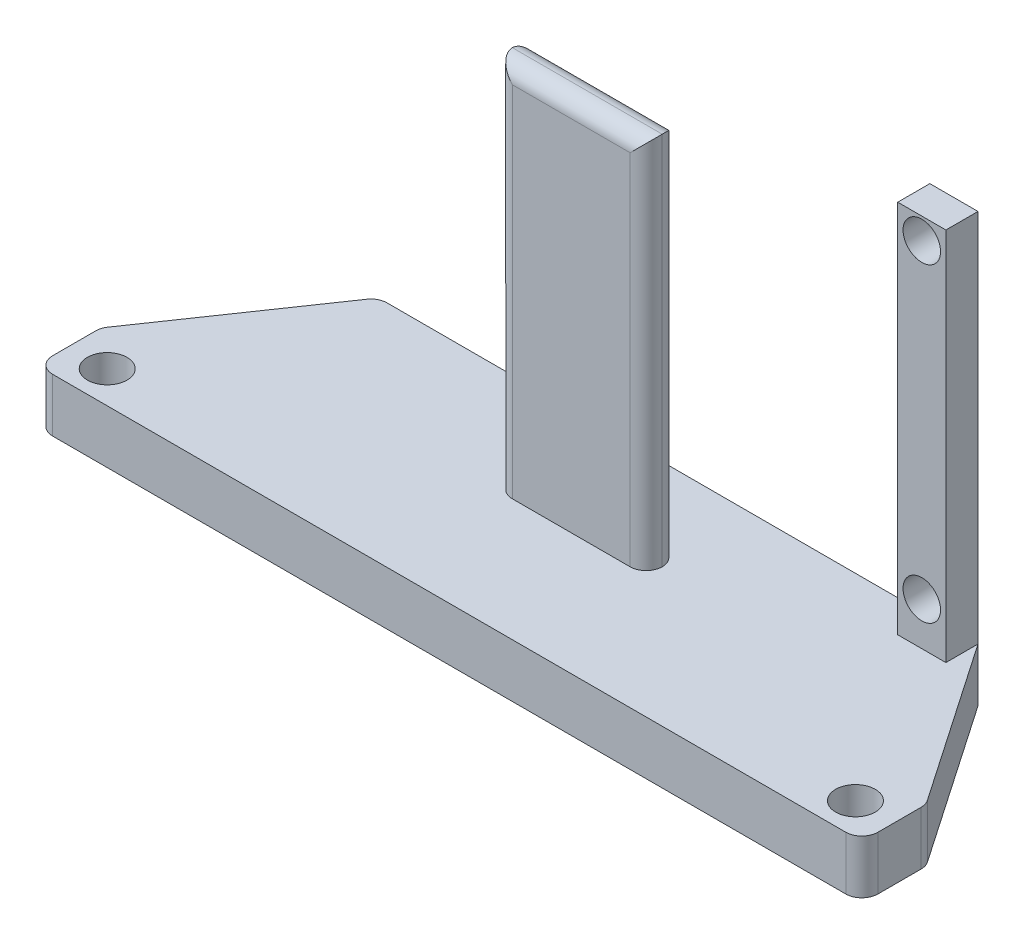
SolidWorks part; units mm, degrees
ref_plane "前视基准面" through (0, 0, 0) normal (0, 0, 1) x (1, 0, 0)
ref_plane "上视基准面" through (0, 0, 0) normal (0, 1, 0) x (1, 0, 0)
ref_plane "右视基准面" through (0, 0, 0) normal (1, 0, 0) x (0, 0, -1)
sketch "草图1" plane through (0, 0, 0) normal (0, 1, 0) x (1, 0, 0)
  line L0 (-38.55, 0) -> (38.55, 0)
  line L2 (28, 21.4) -> (-28, 21.4)
  line L4 (0, -20.2635) -> (0, 37.2321) construction
  line L5 (-38.55, 0) -> (-38.55, 6)
  line L6 (-38.55, 6) -> (-28, 21.4)
  line L7 (38.55, 0) -> (38.55, 6)
  line L8 (38.55, 6) -> (28, 21.4)
  circle A0 centre (-34.95, 3) radius 1.85
  circle A1 centre (34.95, 3) radius 1.85
  point P12 (-38.55, 3)
  point P22 (38.55, 3)
  dimension "D4" = 3.7
  dimension "D7" = 3.7
  dimension "D1" = 77.1
  dimension "D2" = 6
  dimension "D3" = 56
  dimension "D5" = 18.4
  dimension "D6" = 69.9
extrude "凸台-拉伸1" add sketch "草图1" against normal blind 5
sketch "草图2" plane through (0, 0, 0) normal (0, 1, 0) x (1, 0, 0)
  line L0 (28, 21.4) -> (-28, 21.4) construction
  line L1 (28, 21.4) -> (23.5, 21.4)
  line L2 (28, 21.4) -> (28, 18.4)
  line L3 (28, 18.4) -> (23.5, 18.4)
  line L4 (23.5, 21.4) -> (23.5, 18.4)
  line L5 (-7, 14.4) -> (7, 14.4)
  line L6 (-7, 14.4) -> (-7, 11.4)
  line L7 (-7, 11.4) -> (7, 11.4)
  line L8 (7, 14.4) -> (7, 11.4)
  point P11 (0, 14.4)
  dimension "D1" = 4.5
  dimension "D2" = 3
  dimension "D3" = 7
  dimension "D4" = 14
  dimension "D5" = 3
extrude "凸台-拉伸2" add sketch "草图2" along normal blind 35
ref_plane "基准面4" through (0, 0, -21.4) normal (0, 0, 1) x (1, 0, 0)
sketch "草图4" plane through (0, 0, -21.4) normal (0, 0, 1) x (1, 0, 0)
  line L0 (28, 35) -> (23.5, 35) construction
  circle A0 centre (25.75, 33) radius 1.75
  circle A1 centre (25.75, 4) radius 1.75
  point P10 (25.75, 35)
  dimension "D2" = 3.5
  dimension "D4" = 3.5
  dimension "D1" = 2
  dimension "D3" = 29
extrude "切除-拉伸2" cut sketch "草图4" along normal blind 35
fillet "圆角3" radius 1.5 6 edges at (-7, 17.5, -14.4) (-7, 17.5, -11.4) (7, 17.5, -14.4) (7, 17.5, -11.4) (0, 35, -11.4) (0, 35, -14.4)
fillet "圆角4" radius 1.5 5 edges at (38.55, -2.5, 0) (38.55, -2.5, -6) (-28, -2.5, -21.4) (-38.55, -2.5, -6) (-38.55, -2.5, 0)
